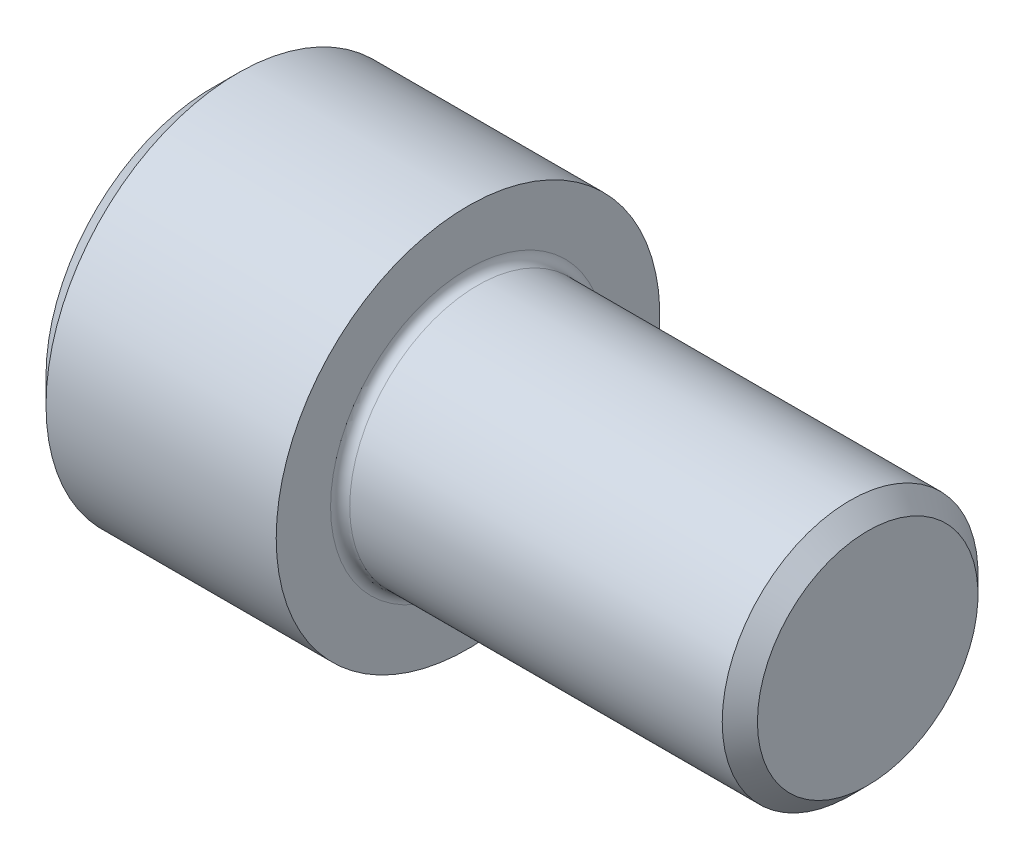
SolidWorks part; units mm, degrees
revolve "Base-Revolve" add sketch "BodySke"
sketch "BodySke" plane through (0, 0, 0) normal (0, 0, 1) x (1, 0, 0)
  line L0 (0, 0) -> (0, 10.4)
  line L1 (1.6, 12) -> (16, 12)
  line L2 (16, 12) -> (16, 8)
  line L3 (16, 8) -> (39.8985, 8)
  line L4 (41, 6.8985) -> (41, 0)
  line L5 (41, 0) -> (0, 0)
  line L6 (-31.75, 0) -> (127, 0) construction
  line L7 (0, 10.4) -> (1.6, 12)
  line L8 (41, 6.8985) -> (39.8985, 8)
  line L9 (0, -10.4) -> (1.6, -12) construction
  line L10 (41, -6.8985) -> (39.8985, -8) construction
  line L11 (18, 9.525) -> (18, 3.175) construction
  line L12 (16, 9.525) -> (16, 3.175) construction
  line L13 (-9, 9.525) -> (-9, 3.175) construction
  dimension "Diameter" = 16
  dimension "Head_ht" = 16
  dimension "Length" = 25
  dimension "Body_ch_ang" = 45
  dimension "Head_dia" = 24
  dimension "Head_ch_ang" = 45
  dimension "Minor_dia" = 13.797
  dimension "Advance" = 2
  dimension "Thread_nom" = 25
  dimension "Thread_length" = 50
  dimension "Head_ch_ht" = 1.6
cosmetic thread "ThreadCosmetic" [suppressed]
fillet "Fillet1" radius 0.6 1 edges at (16, 0, 8)
ref_plane "Plane1" through (0, 0, 0) normal (0, 0, 1) x (1, 0, 0)
ref_plane "Plane2" through (0, 0, 0) normal (0, 1, 0) x (1, 0, 0)
ref_plane "Plane3" through (0, 0, 0) normal (1, 0, 0) x (0, 0, -1)
sketch "Sketch2" plane through (0, 0, 0) normal (0, 0, 1) x (1, 0, 0)
  line L0 (0, 7.071) -> (8, 7.071)
  line L1 (8, 7.071) -> (12.0824, 0)
  line L2 (-31.75, 0) -> (127, 0) construction
  line L3 (12.0824, 0) -> (0, 0)
  line L4 (0, 0) -> (0, 7.071)
  line L5 (0, 10.4) -> (0, -10.4) construction
  line L6 (0, 0) -> (47.625, 0) construction
  line L7 (16, -12) -> (16, 12) construction
  dimension "D1" = 7.071
  dimension "D2" = 60
revolve "Hex-PreBroach" cut sketch "Sketch2" angle 360 about L6
sketch "Sketch3" plane through (0, 0, 0) normal (-1, 0, 0) x (0, 0.5, 0.866)
  line L0 (4.0824, 7.071) -> (-4.0824, 7.071)
  line L1 (-4.0824, 7.071) -> (-8.1649, 0)
  line L2 (4.0824, 7.071) -> (8.1649, 0)
  line L3 (4.0824, -7.071) -> (8.1649, 0)
  line L4 (4.0824, -7.071) -> (-4.0824, -7.071)
  line L5 (-4.0824, -7.071) -> (-8.1649, 0)
  dimension "D1" = 7.071
  dimension "D2" = 7.071
extrude "Hex" cut sketch "Sketch3" against normal blind 8
sketch "Sketch4" plane through (0, 0, 0) normal (-1, 0, 0) x (0, 0, 1)
  line L0 (0, 0) -> (3.7846, 0)
  line L1 (0, 0) -> (6.1484, 3.5498) construction
  line L2 (0, 0) -> (1.8923, 3.2776)
  line L3 (3.1235, 0.8061) -> (3.6229, 1.0945)
  line L4 (2.2599, 2.3019) -> (2.7593, 2.5903)
  arc A0 (3.1235, 0.8061) -> (2.2599, 2.3019) centre (0, 0) ccw
  arc A1 (3.7846, 0) -> (3.6229, 1.0945) centre (0, 0) ccw
  arc A2 (1.8923, 3.2776) -> (2.7593, 2.5903) centre (0, 0) cw
  dimension "D1" = 30
  dimension "D2" = 60
  dimension "Spline_p_dim" = 1.7272
  dimension "D3" = 0.8636
extrude "Spline" [suppressed] cut sketch "Sketch4" against normal blind 8
pattern_circular "CirPattern1" [suppressed] count 6 every 60
sketch "Sketch5" plane through (0, 0, 0) normal (0, 0, 1) x (1, 0, 0)
  line L0 (-31.75, 0) -> (127, 0) construction
  line L2 (0, 10.4) -> (0, -10.4) construction
  circle A0 centre (5, 0) radius 0.825
  dimension "Drilled_hole_dia" = 1.65
  dimension "Drilled_hole_loc" = 5
extrude "Hole" [suppressed] cut sketch "Sketch5" against normal through all and the other way through all
pattern_circular "Drilled-4" [suppressed] count 2 every 60
pattern_circular "Drilled-6" [suppressed] count 3 every 60
sketch "ThdSchSke" plane through (0, 0, 0) normal (0, 0, 1) x (1, 0, 0)
  line L0 (18, -6.8985) -> (17.2287, -8)
  line L1 (18, -6.8985) -> (18.7713, -8)
  line L2 (18.7713, -8) -> (18.7713, -10)
  line L3 (-3.175, 0) -> (5.1513, 0) construction
  line L5 (18.7713, -10) -> (17.2287, -10)
  line L6 (17.2287, -10) -> (17.2287, -8)
  line L7 (0, 10.4) -> (0, -10.4) construction
  dimension "Thread_minor" = 13.797
  dimension "Diameter" = 16
  dimension "Start" = 18
revolve "ThreadSchematic" [suppressed] cut sketch "ThdSchSke" angle 360 about L3
pattern_linear "ThdSchPat" [suppressed]
equation "\"D2@Sketch3\" = \"Hex_size@Sketch3\" / 2"
equation "\"D1@Sketch3\" = \"Hex_size@Sketch3\" / 2"
equation "\"D1@Sketch2\" = \"Hex_size@Sketch3\" / 2"
equation "\"D3@Sketch4\" = \"Spline_p_dim@Sketch4\" / 2"
equation "\"Thread_minor@ThreadCosmetic\"  =  \"Minor_dia@BodySke\""
equation "\"D2@CirPattern1\" = 360 / \"Num_teeth@CirPattern1\""
equation "\"Wall_thickness@Sketch2\" = \"Head_ht@BodySke\" - \"Key_eng@Hex\""
equation "\"Thread_length@ThreadCosmetic\" = ((sgn( (\"Length@BodySke\" - \"Advance@BodySke\" ) - \"Thread_nom@BodySke\" )-1)*( (\"Length@BodySke\" - \"Advance@BodySke\" ) - \"Thread_nom@BodySke\" ))/-2+ \"Thread_nom@BodySke\""
equation "\"Thread_minor@ThdSchSke\" = \"Minor_dia@BodySke\""
equation "\"Diameter@ThdSchSke\" = \"Diameter@BodySke\""
equation "\"Overcut@ThdSchSke\" = \"Diameter@BodySke\" * 1.25"
equation "\"Start@ThdSchSke\" = \"Head_ht@BodySke\" + \"Length@BodySke\" - \"Thread_length@ThreadCosmetic\"  '---Non-countersunk---"
equation "\"Num_threads@ThdSchPat\" = int( \"Thread_length@ThreadCosmetic\" / \"Advance@BodySke\" + 0.999 )  + 1"
equation "\"Advance@ThdSchPat\" = \"Thread_length@ThreadCosmetic\" /  (\"Num_threads@ThdSchPat\" - 1) 'relax it"
equation "\"Num_threads@ThdSchPat\" = \"Num_threads@ThdSchPat\" - sgn( \"Num_threads@ThdSchPat\" - 1) '---chamfered tips only---"
